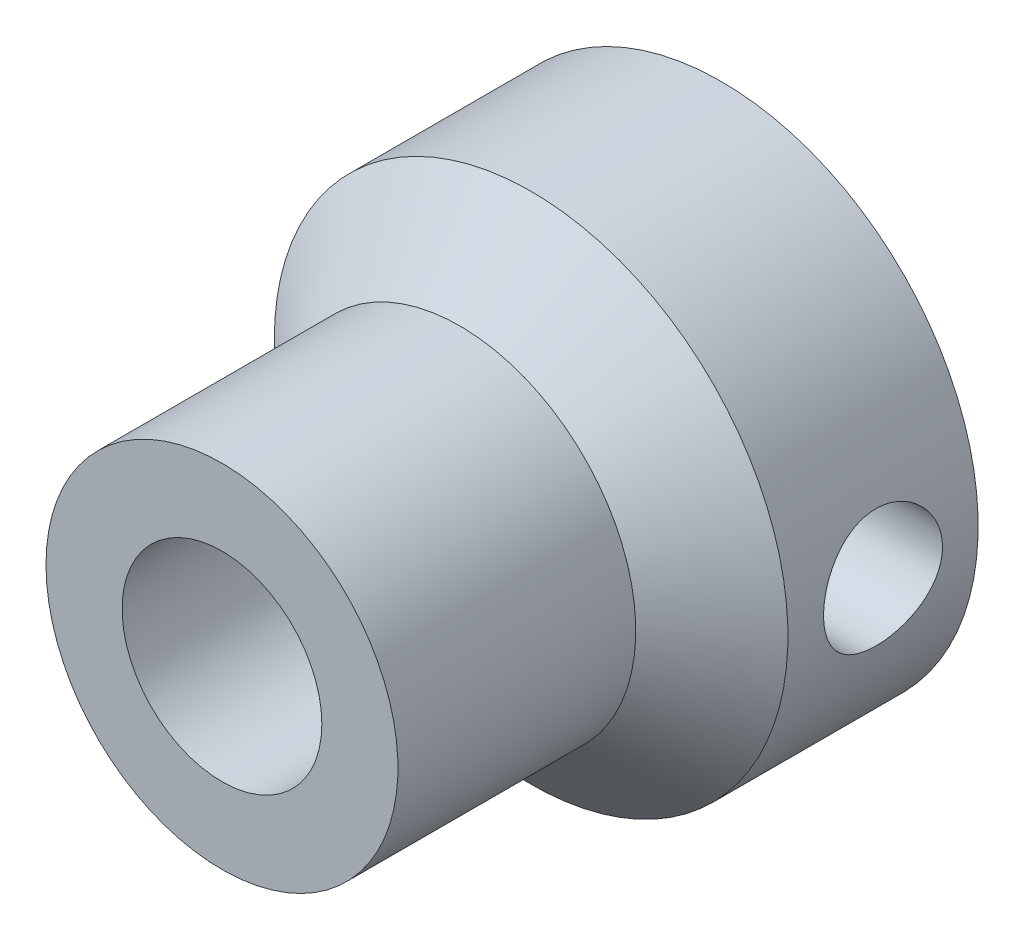
SolidWorks part; units mm, degrees
ref_plane "Top" through (0, 0, 0) normal (0, 0, 1) x (1, 0, 0)
ref_plane "Front" through (0, 0, 0) normal (0, 1, 0) x (1, 0, 0)
ref_plane "Right" through (0, 0, 0) normal (1, 0, 0) x (0, 0, -1)
ref_plane "Base Tangent Plane" through (5.4, 0, 0) normal (1, 0, 0) x (0, 0, -1)
sketch "Body Sketch" plane through (0, 0, 0) normal (0, 1, 0) x (-1, 0, 0)
  line L1 (1, 10.5) -> (3.7, 10.5)
  line L2 (3.7, 10.5) -> (3.7, 5.5)
  line L3 (3.7, 5.5) -> (5.4, 4)
  line L4 (5.4, 4) -> (5.4, 0)
  line L5 (5.4, 0) -> (2.5, 0)
  line L8 (0, 0) -> (0, 10.5) construction
  line L9 (1, 10.5) -> (1, 5)
  line L10 (1, 5) -> (2.5, 5)
  line L11 (2.5, 5) -> (2.5, 0)
  dimension "D1" = 4
  dimension "D6" = 5
  dimension "D2" = 10.5
  dimension "D4" = 5.4
  dimension "D3" = 3.7
  dimension "D5" = 2.5
  dimension "D7" = 1
  dimension "D8" = 5
revolve "Body Revolve" add sketch "Body Sketch" angle 360 about L8
hole_wizard "Connector M5x0.8 Tapped Hole" positions "Connector Position Sketch" profile "Sketch5" tap size "M5x0.8" standard "ANSI Metric" end condition through all
sketch "Connector Position Sketch" plane through (0, 0, 10.5) normal (0, 0, 1) x (1, 0, 0)
  point P0 (0, 0)
cosmetic thread "Connector Hole Thread"
sketch "Sketch5" plane through (0, 0, 10.5) normal (1, 0, 0) x (0, -1, 0)
  line L0 (0, 0) -> (0, 10.5)
  line L1 (0, 10.5) -> (2.1, 10.5)
  line L2 (2.1, 10.5) -> (2.1, 0)
  line L5 (2.1, 0) -> (0, 0)
  line L11 (0, -6.35) -> (0, 107.95) construction
  dimension "Thru Tap Drill Dia." = 4.2
  dimension "Thru Tap Drill Depth" = 10.5
hole_wizard "Set Screw 1 M3x0.5 Tapped Hole" positions "Set Screw Position Sketch" profile "Set Screw Profile Sketch" tap size "M3x0.5" standard "ANSI Metric" end condition up to next
sketch3d "Set Screw Position Sketch"
  point P0 (5.4, 0, 2)
  dimension "D1" = 2
sketch "Set Screw Profile Sketch" plane through (5.4, 0, 2) normal (0, 1, 0) x (0, 0, -1)
  line L0 (0, 0) -> (0, 2.9)
  line L1 (0, 2.9) -> (1.25, 2.9)
  line L2 (1.25, 2.9) -> (1.25, 0)
  line L5 (1.25, 0) -> (0, 0)
  line L11 (0, -6.35) -> (0, 107.95) construction
  dimension "Thru Tap Drill Dia." = 2.5
  dimension "Thru Tap Drill Depth" = 2.9
cosmetic thread "Set Screw 1 Hole Thread"
pattern_circular "Set Screw 2 Pattern" count 2 over 360 about axis through (0, 0, 0) along (0, 0, 1) of "Set Screw 1 M3x0.5 Tapped Hole" reverse direction yes
cosmetic thread "Hole Thread3"
equation "\"Base Diameter\"= 10.8"
equation "\"D4@Body Sketch\"=\"Base Diameter\"/2"
equation "\"D1@Base Tangent Plane\"=\"Base Diameter\"/2"
